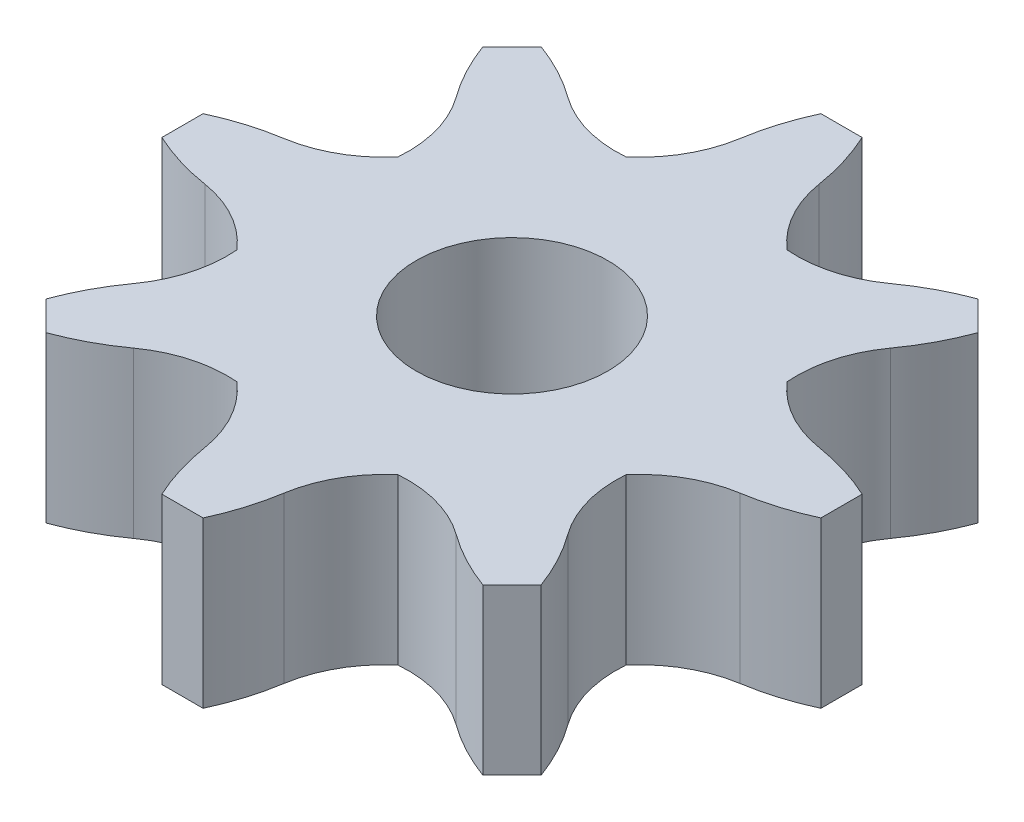
SolidWorks part; units mm, degrees
ref_plane "Front Plane" through (0, 0, 0) normal (0, 0, 1) x (1, 0, 0)
ref_plane "Top Plane" through (0, 0, 0) normal (0, 1, 0) x (1, 0, 0)
ref_plane "Right Plane" through (0, 0, 0) normal (1, 0, 0) x (0, 0, -1)
sketch "Sketch1" plane through (0, 0, 0) normal (0, 1, 0) x (1, 0, 0)
  line L2 (0.5, 7.9938) -> (-0.5, 7.9938)
  line L3 (-1, 4.9938) -> (1, 4.9938)
  line L4 (0, 7.9938) -> (0, 4.9938)
  line L6 (0, -2.325) -> (0, 2.325)
  line L7 (-0.8849, -2.15) -> (0.8849, -2.15)
  line L8 (0, 6.4938) -> (0.9583, 6.4938)
  line L9 (0, 6.4938) -> (-0.9583, 6.4938)
  line L10 (-2, 4.6838) -> (2, 4.6838)
  circle A0 centre (0, 0) radius 5.093
  arc A1 (-1, 4.9938) -> (-0.5, 7.9938) centre (4.6965, 5.5861) cw
  arc A2 (0.5, 7.9938) -> (1, 4.9938) centre (-4.6965, 5.5861) cw
  circle A3 centre (0, 0) radius 2.325
  arc A4 (-0.9583, 6.4938) -> (-2, 4.6838) centre (-3.8614, 6.9598) cw
  arc A5 (0.9583, 6.4938) -> (2, 4.6838) centre (3.8614, 6.9598) ccw
  point P23 (0, 0)
  point P24 (4.6965, 5.5861)
  dimension "D4" = 5.7272
  dimension "D5" = 10.1859
  dimension "D6" = 4.65
  dimension "D1" = 3
  dimension "D2" = 2
  dimension "D3" = 1
  dimension "D7" = 0.175
  dimension "D8" = 4
extrude "Boss-Extrude1" add sketch "Sketch1" along normal blind 4 contours A1 L2 A2 L3 | L10 A5 L8 L9 A4
sketch "Sketch4" plane through (0, 0, 0) normal (1, 0, 0) x (0, 0, -1)
  line L0 (0, 0) -> (0, 7.6311)
pattern_circular "CirPattern2" count 8 over 360 about axis through (0, 0, 0) along (0, 1, 0) of "Boss-Extrude1" reverse direction yes
extrude "Boss-Extrude3" add sketch "Sketch1<5>" along normal blind 4 contours L10 A0 A3 region at (4.1321, 0, -2.7286)
sketch "Sketch1<5>" plane through (0, 0, 0) normal (0, 1, 0) x (1, 0, 0) same geometry as "Sketch1"
equation "\"teeth\"= 8'num of teeth in gear"
equation "\"gearRadius\"= \"teeth\" * 4 / ( 2 * Pi )"
equation "\"D5@Sketch1\"=\"gearRadius\"*2"
equation "\"D1@CirPattern2\"=\"teeth\""
equation "\"thickness\" = 6"
equation "\"D1@Boss-Extrude1\"=\"thickness\""
equation "\"D1@Boss-Extrude3\"=\"thickness\""
